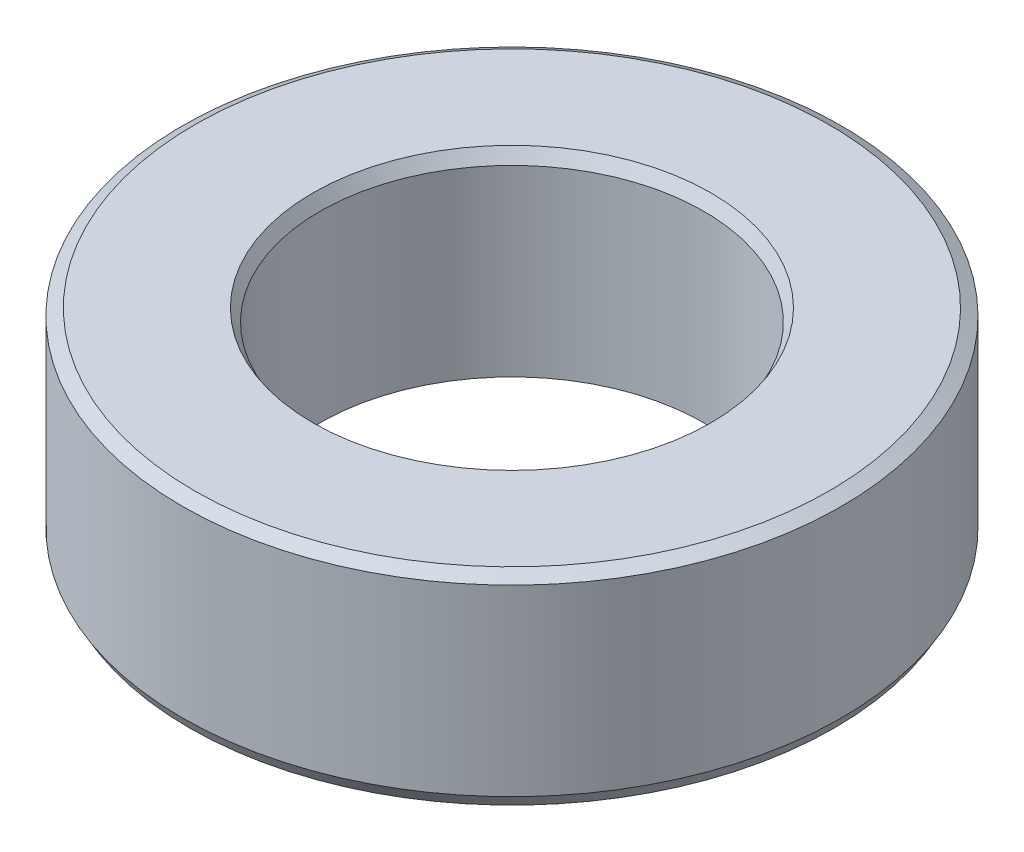
SolidWorks part; units mm, degrees
ref_plane "Front Plane" through (0, 0, 0) normal (0, 0, 1) x (1, 0, 0)
ref_plane "Top Plane" through (0, 0, 0) normal (0, 1, 0) x (1, 0, 0)
ref_plane "Right Plane" through (0, 0, 0) normal (1, 0, 0) x (0, 0, -1)
sketch "Sketch1" plane through (0, 0, 0) normal (0, 1, 0) x (1, 0, 0)
  circle A0 centre (0, 0) radius 50
  dimension "SLEEVE_OD" = 100
extrude "Boss-Extrude1" add sketch "Sketch1" along normal blind 30.7495
sketch "Sketch2" plane through (0, 0, 0) normal (0, 1, 0) x (1, 0, 0)
  circle A0 centre (0, 0) radius 29.1245
  dimension "BORE_D" = 58.2489
extrude "Cut-Extrude1" cut sketch "Sketch2" along normal through all
chamfer "Chamfer1" distance 1.0819 angle 60 4 edges at (0, 30.7495, 29.1245) (0, 0, 29.1245) (0, 0, 50) (0, 30.7495, 50) first distance on face at (0, 30.7495, 29.1245) first distance on face at (0, 0, 29.1245) first distance on face at (0, 30.7495, 50)
